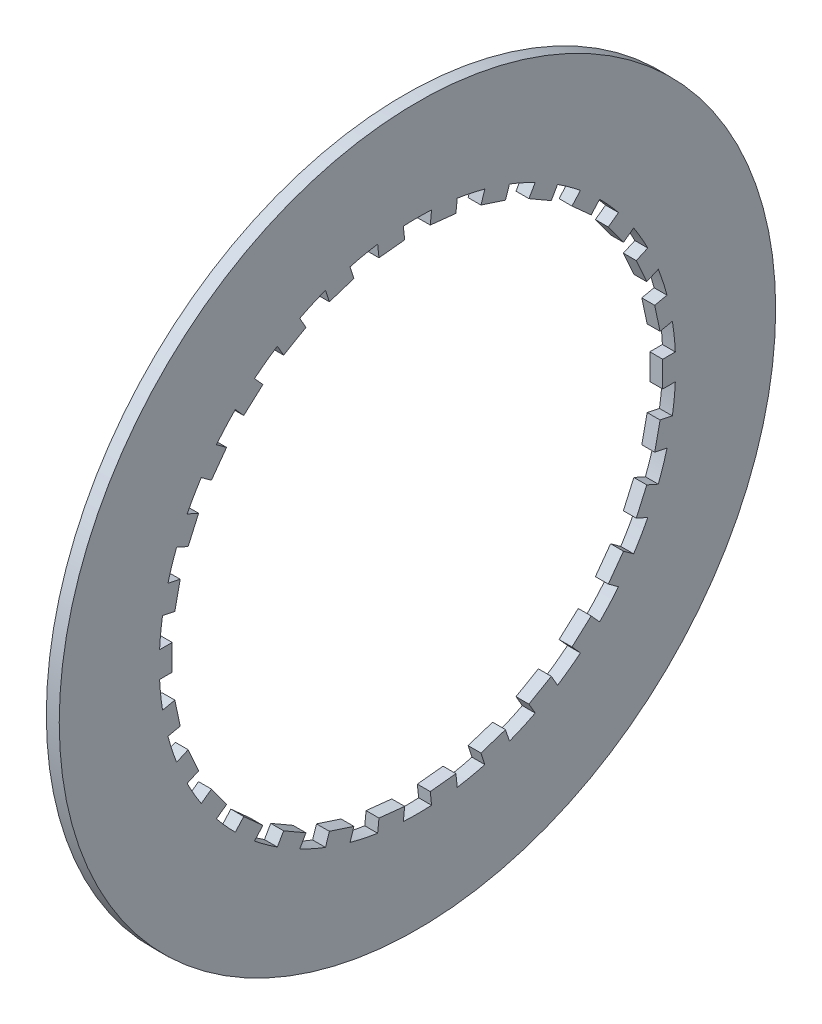
SolidWorks part; units mm, degrees
material "AISI 1075 spring steel"
ref_plane "Front Plane" through (0, 0, 0) normal (1, 0, 0) x (0, 1, 0)
ref_plane "Top Plane" through (0, 0, 0) normal (0, 0, 1) x (0, 1, 0)
ref_plane "Right Plane" through (0, 0, 0) normal (0, 1, 0) x (-1, 0, 0)
sketch "Sketch1" plane through (0, 0, 0) normal (1, 0, 0) x (0, 1, 0)
  line L0 (0, 65.2724) -> (0, 0) construction
  line L1 (-11.1451, 0) -> (6.3855, 0) construction
  line L2 (-2, 38) -> (2, 38)
  line L3 (-2, 38) -> (-2, 40)
  line L5 (2, 38) -> (2, 41.2393)
  circle A0 centre (0, 0) radius 55.5
  circle A1 centre (0, 0) radius 40
  dimension "D1" = 111
  dimension "D2" = 80
  dimension "D5" = 38
  dimension "D3" = 4
  dimension "D4" = 2
extrude "Boss-Extrude1" add sketch "Sketch1" along normal blind 2 contours A0 A1 region at (0, -53.9302, 0)
extrude "Boss-Extrude2" add sketch "Sketch1<3>" along normal blind 2 contours L5 A1 L3 L2 region at (0, 0, 38.9917)
sketch "Sketch1<3>" plane through (0, 0, 0) normal (1, 0, 0) x (0, 1, 0) same geometry as "Sketch1"
pattern_circular "CirPattern1" count 30 over 360 about axis through (2, 0, 0) along (1, 0, 0) of "Boss-Extrude2"
ref_axis "Axis1" through (-0.1, 0, 0) along (1, 0, 0)
